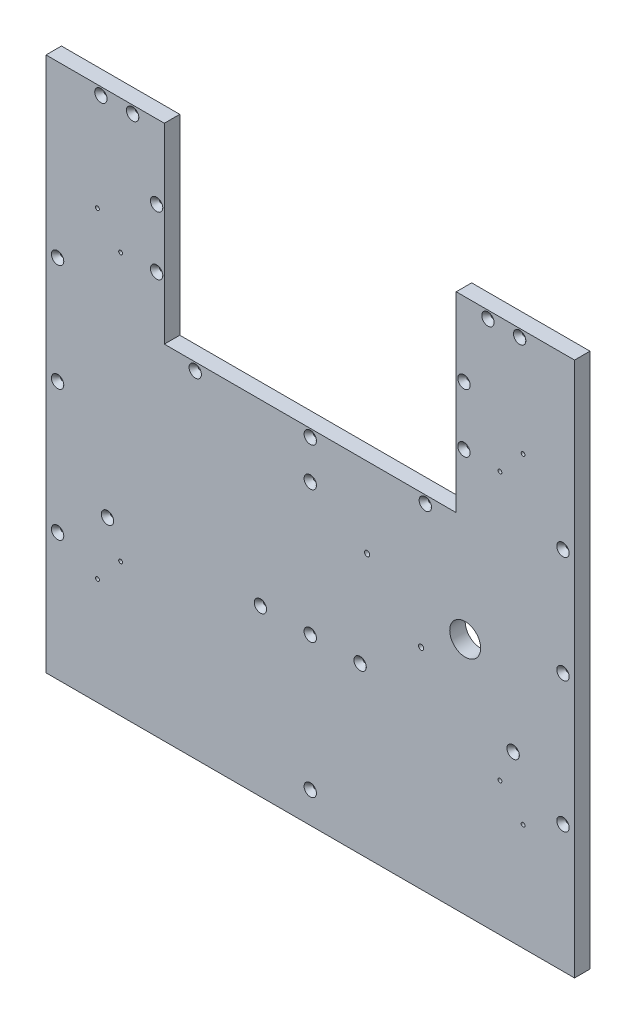
SolidWorks part; units mm, degrees
material "Beech"
ref_plane "Front Plane" through (0, 0, 0) normal (0, 0, 1) x (1, 0, 0)
ref_plane "Top Plane" through (0, 0, 0) normal (0, 1, 0) x (1, 0, 0)
ref_plane "Right Plane" through (0, 0, 0) normal (1, 0, 0) x (0, 0, -1)
sketch "Sketch1" plane through (0, 0, 0) normal (0, 0, 1) x (1, 0, 0)
  line L0 (341.3045, 12.7) -> (244.0045, 12.7)
  line L2 (341.3045, 12.7) -> (244.0045, 12.7) construction
  line L3 (244.0045, 12.7) -> (244.0045, -144.6)
  line L4 (244.0045, -144.6) -> (124.0045, -144.6)
  line L5 (341.3045, -455.5295) -> (-93.2955, -455.5295) construction
  line L6 (124.0045, -144.6) -> (124.0045, -427.3421)
  line L7 (124.0045, -427.3421) -> (341.3045, -427.3421)
  line L8 (341.3045, -427.3421) -> (341.3045, 12.7)
  line L12 (16.7045, -144.6) -> (231.3045, -144.6) construction
  point P18 (124.0045, -144.6)
  dimension "D1" = 28.1874
extrude "Boss-Extrude1" add sketch "Sketch1" along normal blind 12.7
mirror "Mirror1" about plane through (124.0045, -144.6, 12.7) normal (1, 0, 0) of "Boss-Extrude1"
hole_wizard "Hole1" positions "Sketch2" profile "Sketch3" legacy
sketch "Sketch2" plane through (124.0045, 10.4243, 12.7) normal (0, 0, 1) x (-1, 0, 0)
  line L12 (0, 0) -> (0, 155.0243) construction
  point P0 (-207.775, 333.0214)
  point P3 (-207.775, 225.489)
  point P6 (-207.775, 137.4243)
  point P9 (-172.1667, 4.0743)
  point P12 (-146.0833, 4.0743)
  point P15 (-94.6, 161.3743)
  point P18 (0, 161.3743)
  point P21 (94.6, 161.3743)
  point P24 (146.0833, 4.0743)
  point P27 (172.1667, 4.0743)
  point P30 (207.775, 137.4243)
  point P33 (207.775, 225.489)
  point P36 (207.775, 333.0214)
  point P39 (166.7958, 301.9704)
  point P42 (40.9792, 301.9704)
  point P45 (-40.9792, 301.9704)
  point P48 (-166.7958, 301.9704)
  point P51 (0, 193.1243)
  point P54 (0, 301.9704)
  point P57 (0, 412.3664)
  point P80 (-126.35, 106.8243)
  point P82 (-126.35, 58.6243)
  point P96 (126.35, 58.6243)
  point P97 (126.35, 106.8243)
sketch "Sketch3" plane through (331.7795, -322.5971, 12.7) normal (1, 0, 0) x (0, -1, 0)
  line L0 (0, 0) -> (0, 32.7039)
  line L1 (0, 32.7039) -> (1.5875, 31.75)
  line L2 (1.5875, 31.75) -> (1.5875, 4.0177)
  line L3 (1.5875, 4.0177) -> (5.08, 0)
  line L4 (5.08, 0) -> (0, 0)
  line L5 (0, -14.3089) -> (0, 102.4216) construction
  line L6 (0, 32.7039) -> (-1.5875, 31.75) construction
  line L7 (-1.5875, 4.0177) -> (-5.08, 0) construction
  dimension "Diameter" = 3.175
  dimension "Depth" = 31.75
  dimension "C-Sink Diameter" = 10.16
  dimension "C-Sink Angle" = 82
  dimension "Drill Angle" = 118
hole_wizard "Hole2" positions "Sketch4" profile "Sketch5" legacy
sketch "Sketch4" plane through (124.0045, 10.4243, 0) normal (0, 0, -1) x (1, 0, 0)
  line L8 (155.95, -2.2757) -> (155.95, 437.7664) construction
  line L11 (175, -2.2757) -> (175, 437.7664) construction
  line L15 (155.95, -2.2757) -> (155.95, 107.7348)
  line L16 (155.95, 107.7348) -> (155.95, 217.7454)
  line L17 (155.95, 217.7454) -> (155.95, 327.7559)
  line L18 (155.95, 327.7559) -> (155.95, 437.7664)
  line L20 (175, -2.2757) -> (175, 85.7327)
  line L21 (175, 85.7327) -> (175, 173.7411)
  line L22 (175, 173.7411) -> (175, 261.7496)
  line L23 (175, 261.7496) -> (175, 349.758)
  line L24 (175, 349.758) -> (175, 437.7664)
  line L25 (0, 155.0243) -> (0, 437.7664) construction
  point P36 (155.95, 107.7348)
  point P40 (155.95, 327.7559)
  point P46 (175, 85.7327)
  point P52 (175, 349.758)
  point P77 (-175, 349.758)
  point P80 (-175, 85.7327)
  point P81 (-155.95, 327.7559)
  point P83 (-155.95, 107.7348)
sketch "Sketch5" plane through (-31.9455, -97.3105, 0) normal (1, 0, 0) x (0, 1, 0)
  line L0 (0, 0) -> (0, 32.7039)
  line L1 (0, 32.7039) -> (1.5875, 31.75)
  line L2 (1.5875, 31.75) -> (1.5875, 4.0177)
  line L3 (1.5875, 4.0177) -> (5.08, 0)
  line L4 (5.08, 0) -> (0, 0)
  line L5 (0, -14.3089) -> (0, 102.4216) construction
  line L6 (0, 32.7039) -> (-1.5875, 31.75) construction
  line L7 (-1.5875, 4.0177) -> (-5.08, 0) construction
  dimension "Diameter" = 3.175
  dimension "Depth" = 31.75
  dimension "C-Sink Diameter" = 10.16
  dimension "C-Sink Angle" = 82
  dimension "Drill Angle" = 118
hole_wizard "1 (1) Diameter Hole1" positions "Sketch6" profile "Sketch7" hole size "1" standard "ANSI Inch" end condition up to next
sketch "Sketch6" plane through (0, 0, 0) normal (0, 0, -1) x (-1, 0, 0)
  line L0 (-270.4295, -231.122) -> (-251.3795, -231.122) construction
  point P0 (-251.3795, -231.122)
  point P8 (0, 0)
  point P9 (-275.0782, -236.8281)
  point P10 (-270.4295, -237.1291)
  dimension "D1" = 19.05
sketch "Sketch7" plane through (251.3795, -231.122, 0) normal (1, 0, 0) x (0, 1, 0)
  line L0 (0, 0) -> (0, 12.7)
  line L1 (0, 12.7) -> (12.7, 12.7)
  line L2 (12.7, 12.7) -> (12.7, 0)
  line L5 (12.7, 0) -> (0, 0)
  line L11 (0, -6.35) -> (0, 107.95) construction
  dimension "Thru Hole Dia." = 25.4
  dimension "Thru Hole Depth" = 12.7
hole_wizard "#6 Clearance Hole1" positions "Sketch8" profile "Sketch9" hole size "#6" standard "ANSI Inch" end condition up to next
sketch "Sketch8" plane through (0, 0, 0) normal (0, 0, -1) x (-1, 0, 0)
  point P0 (-215.1525, -254.8561)
  point P2 (-170.7025, -210.4061)
sketch "Sketch9" plane through (215.1525, -254.8561, 0) normal (1, 0, 0) x (0, 1, 0)
  line L0 (0, 0) -> (0, 12.7)
  line L1 (0, 12.7) -> (2.1526, 12.7)
  line L2 (2.1526, 12.7) -> (2.1526, 0)
  line L5 (2.1526, 0) -> (0, 0)
  line L11 (0, -6.35) -> (0, 107.95) construction
  dimension "Thru Hole Dia." = 4.3053
  dimension "Thru Hole Depth" = 12.7
